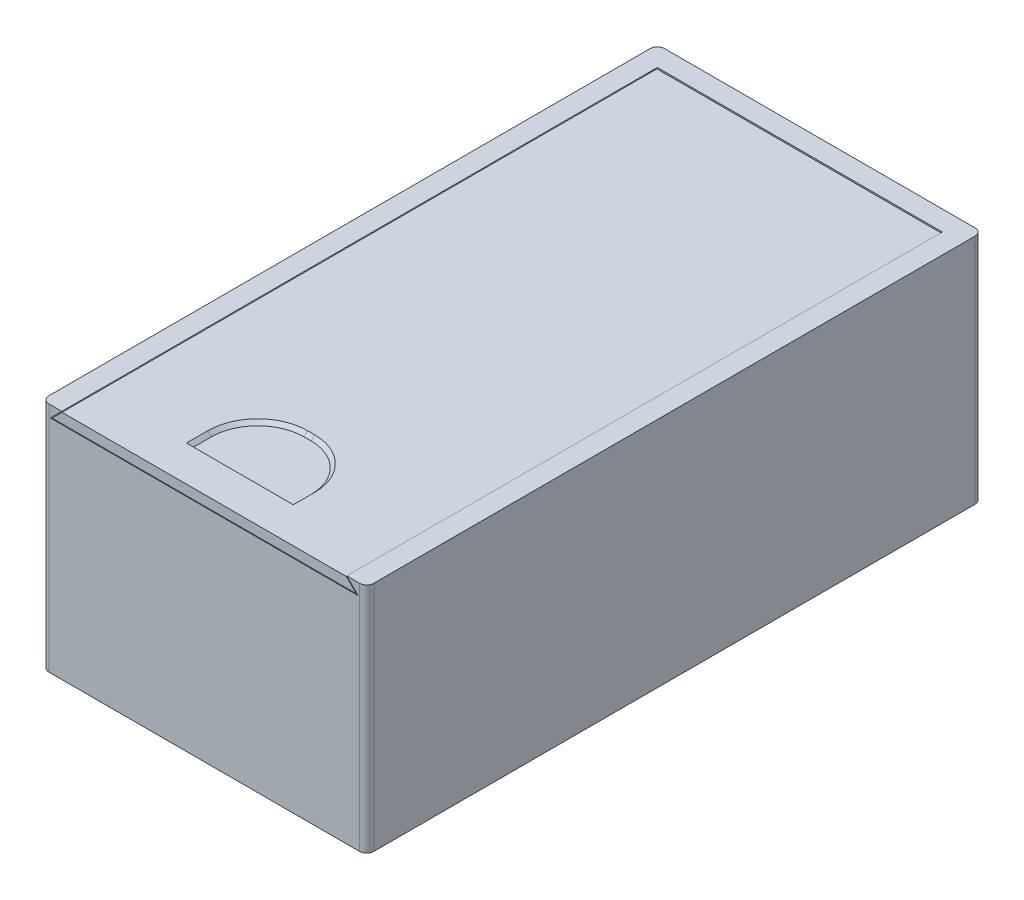
SolidWorks part; units mm, degrees
ref_plane "Front Plane" through (0, 0, 0) normal (0, 0, 1) x (1, 0, 0)
ref_plane "Top Plane" through (0, 0, 0) normal (0, 1, 0) x (1, 0, 0)
ref_plane "Right Plane" through (0, 0, 0) normal (1, 0, 0) x (0, 0, -1)
sketch "Sketch1" plane through (0, 0, 0) normal (0, 0, 1) x (1, 0, 0)
  line L1 (-22.8, -16.3) -> (22.8, -16.3)
  line L2 (-22.8, -16.3) -> (-22.8, 16.3)
  line L3 (-22.8, 16.3) -> (22.8, 16.3)
  line L4 (22.8, -16.3) -> (22.8, 16.3)
  line L5 (-22.8, -16.3) -> (22.8, 16.3) construction
  line L6 (-22.8, 16.3) -> (22.8, -16.3) construction
  point P0 (0, 0)
  dimension "D1" = 32.6
  dimension "D2" = 45.6
extrude "Boss-Extrude1" add sketch "Sketch1" along normal blind 86.4
shell "Shell1" thickness 2.8 removed face at (0, 16.3, 43.2)
sketch "Sketch2" plane through (0, 0, 86.4) normal (0, 0, 1) x (1, 0, 0)
  line L0 (20, 16.3) -> (-20, 16.3) construction
  line L1 (20, 16.3) -> (-20, 16.3)
  line L2 (-20, 16.3) -> (-21.6, 14.7)
  line L3 (-21.6, 14.7) -> (21.6, 14.7)
  line L4 (21.6, 14.7) -> (20, 16.3)
  line L5 (22.8, 16.3) -> (-22.8, 16.3) construction
  line L6 (-22.8, 16.3) -> (-22.8, -16.3) construction
  dimension "D1" = 45
  dimension "D2" = 45
  dimension "D3" = 1.2
extrude "Cut-Extrude1" cut sketch "Sketch2" against normal up to surface (83.6 mm away) up to face at (0, 1.4, 2.8)
sketch "Sketch3" plane through (0, 0, 86.4) normal (0, 0, 1) x (1, 0, 0)
  line L8 (19.9586, 16.2) -> (-19.9586, 16.2)
  line L9 (-19.9586, 16.2) -> (-21.3586, 14.8)
  line L10 (-21.3586, 14.8) -> (21.3586, 14.8)
  line L11 (21.3586, 14.8) -> (19.9586, 16.2)
  line L12 (19.9586, 16.2) -> (-19.9586, 16.2)
  line L13 (-19.9586, 16.2) -> (-21.3586, 14.8)
  line L14 (-21.3586, 14.8) -> (21.3586, 14.8)
  line L15 (21.3586, 14.8) -> (19.9586, 16.2)
  dimension "D1" = 0.1
extrude "Boss-Extrude2" add sketch "Sketch3" against normal offset from surface (83.5 mm away) 0.1 separate body up to face at (0, 8.05, 2.8)
sketch "Sketch5" plane through (0, 16.2, 0) normal (0, 1, 0) x (1, 0, 0)
  line L0 (0, -1118.4) -> (0, 48881.6) construction
  line L1 (19.9586, -86.4) -> (-19.9586, -86.4) construction
  line L3 (-7.5, -81.4) -> (7.5, -81.4)
  line L4 (-7.5, -81.4) -> (-7.5, -71.4)
  line L5 (-7.5, -71.4) -> (7.5, -71.4)
  line L6 (7.5, -81.4) -> (7.5, -71.4)
  line L7 (-7.5, -81.4) -> (7.5, -71.4) construction
  line L8 (-7.5, -71.4) -> (7.5, -81.4) construction
  point P1 (0, -76.4)
  point P5 (0, -86.4)
  dimension "D1" = 5
  dimension "D2" = 15
  dimension "D3" = 10
extrude "Cut-Extrude3" cut sketch "Sketch5" against normal blind 0.5
fillet "Fillet1" radius 7 2 edges at (-7.5, 15.95, 71.4) (7.5, 15.95, 71.4)
chamfer "Chamfer1" distance 0.5 angle 45 5 edges at (7.5, 15.7, 79.9) (5.4497, 15.7, 73.4503) (0, 15.7, 71.4) (-7.5, 15.7, 79.9) (-5.4497, 15.7, 73.4503)
fillet "Fillet2" radius 1 4 edges at (-22.8, 0, 0) (22.8, 0, 0) (-22.8, 0, 86.4) (22.8, 0, 86.4)
equation "\"D1@Boss-Extrude1\"=78+2.8*3"
equation "\"D2@Sketch1\"=40+2.8*2"
equation "\"D1@Sketch1\"=23.00mm+9.6"
